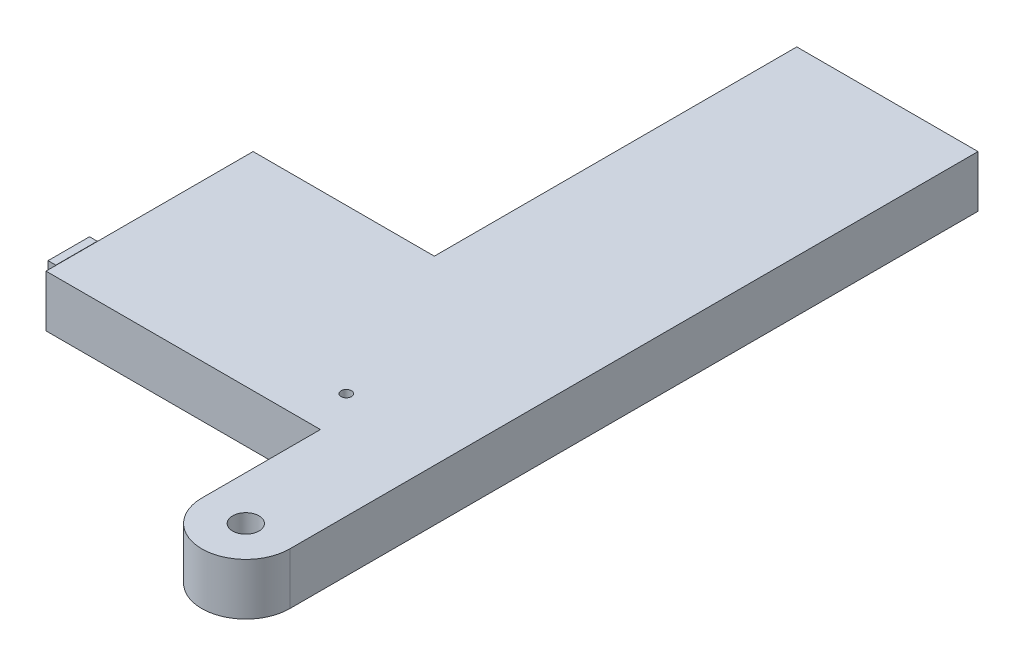
SolidWorks part; units mm, degrees
ref_plane "Front Plane" through (0, 0, 0) normal (0, 0, 1) x (1, 0, 0)
ref_plane "Top Plane" through (0, 0, 0) normal (0, 1, 0) x (1, 0, 0)
ref_plane "Right Plane" through (0, 0, 0) normal (1, 0, 0) x (0, 0, -1)
sketch "CornerrSketch1" plane through (0, 0, 0) normal (0, 1, 0) x (1, 0, 0)
  line L0 (0, 0) -> (0, 80)
  line L5 (0, 80) -> (70, 80)
  line L6 (70, 80) -> (70, 220)
  line L7 (140, 220) -> (70, 220)
  line L8 (106, -45.825) -> (106, 0)
  line L9 (0, 0) -> (106, 0)
  line L10 (140, 220) -> (140, -45.825)
  arc A0 (106, -45.825) -> (140, -45.825) centre (123, -45.825) ccw
  dimension "D5" = 34
  dimension "D4" = 80
  dimension "D3" = 70
  dimension "D1" = 220
  dimension "D2" = 45.825
  dimension "D6" = 140
extrude "CornerBoss-Extrude1" add sketch "CornerrSketch1" along normal blind 20
shell "Shell1" thickness 3 removed face at (79, 0, -61.4188)
sketch "PadSketch1" plane through (0, 17, 0) normal (0, -1, 0) x (1, 0, 0)
  line L1 (0, 0) -> (106, 0) construction
  line L2 (140, 45.825) -> (140, -220) construction
  circle A0 centre (99, -17) radius 5
  circle A1 centre (123, 45.825) radius 12
  dimension "D1" = 10
  dimension "D4" = 24
  dimension "D3" = 17
  dimension "D2" = 41
extrude "PadBoss-Extrude1" add sketch "PadSketch1" along normal blind 10
sketch "StepperShaftCut-Sketch3" plane through (0, 7, 0) normal (0, -1, 0) x (1, 0, 0)
  circle A0 centre (123, 45.825) radius 5.1
  circle A1 centre (99, -17) radius 2
  dimension "D1" = 10.2
  dimension "D2" = 4
extrude "StepperShaftCut-Extrude1" cut sketch "StepperShaftCut-Sketch3" against normal through all
sketch "ThreadedNutMountHolesSketch5" plane through (0, 7, 0) normal (0, -1, 0) x (1, 0, 0)
  circle A0 centre (123, 53.825) radius 1
  circle A1 centre (131, 45.825) radius 1
  circle A2 centre (115, 45.825) radius 1
  circle A3 centre (123, 37.825) radius 1
  dimension "D3" = 2
  dimension "D1" = 8
  dimension "D2" = 16
  dimension "D4" = 8
  dimension "D5" = 16
extrude "ThreadedNutMountHolesCut-Extrude2" cut sketch "ThreadedNutMountHolesSketch5" against normal blind 10
sketch "TopPegHoleSketch4" plane through (0, 0, -220) normal (0, 0, -1) x (-1, 0, 0)
  line L1 (-130, 14) -> (-120, 14)
  line L2 (-130, 14) -> (-130, 0)
  line L3 (-130, 0) -> (-120, 0)
  line L4 (-120, 14) -> (-120, 0)
  line L5 (-140, 0) -> (-70, 0) construction
  line L6 (-140, 20) -> (-140, 0) construction
  dimension "D2" = 10
  dimension "D3" = 14
  dimension "D1" = 10
extrude "TopPegHoleCut-Extrude2" cut sketch "TopPegHoleSketch4" against normal blind 3
sketch "BLPegSketch5" plane through (0, 0, 0) normal (-1, 0, 0) x (0, 0, 1)
  line L1 (-19.9, 13.9) -> (-10.1, 13.9)
  line L2 (-19.9, 13.9) -> (-19.9, 0)
  line L3 (-19.9, 0) -> (-10.1, 0)
  line L4 (-10.1, 13.9) -> (-10.1, 0)
  line L5 (-80, 0) -> (0, 0) construction
  line L6 (0, 20) -> (0, 0) construction
  dimension "D2" = 13.9
  dimension "D3" = 9.8
  dimension "D1" = 10.1
extrude "BLPegBoss-Extrude3" add sketch "BLPegSketch5" along normal blind 3.1
sketch "BLPegCapSketch6" plane through (-3.1, 0, 0) normal (-1, 0, 0) x (0, 0, 1)
  line L0 (-19.9, 13.9) -> (-19.9, 0) construction
  line L1 (-22.9, 17) -> (-6.9, 17)
  line L2 (-22.9, 17) -> (-22.9, 0)
  line L3 (-22.9, 0) -> (-6.9, 0)
  line L4 (-6.9, 17) -> (-6.9, 0)
  line L8 (-19.9, 0) -> (-10.1, 0) construction
  dimension "D1" = 16
  dimension "D3" = 17
  dimension "D2" = 3
extrude "BLPegCapBoss-Extrude4" add sketch "BLPegCapSketch6" along normal blind 3
sketch "BedCenterPegHoleCutSketch1" plane through (70, 0, 0) normal (-1, 0, 0) x (0, 0, 1)
  line L0 (-220, 0) -> (-80, 0) construction
  line L1 (-190, 14) -> (-180, 14)
  line L2 (-190, 14) -> (-190, 0)
  line L3 (-190, 0) -> (-180, 0)
  line L4 (-180, 14) -> (-180, 0)
  line L5 (-80, 20) -> (-80, 0) construction
  dimension "D2" = 10
  dimension "D1" = 14
  dimension "D3" = 100
extrude "BedCenterPegHoleCut-Extrude1" cut sketch "BedCenterPegHoleCutSketch1" against normal blind 3
equation "\"BedThickness\"= 20mm"
equation "\"BedToBuildPlateStandoffHolesDistanceFromLeftOrRight\"= \"BuildPlateStandoffHolesDistanceFromLeftOrRight\" + \"BedIncreasedByWidth\" / 2'Equals 17"
equation "\"BedLLongSide\"= \"BedThirdSize\" * 3'Equals 210"
equation "\"BedLShortSide\"= \"BedThirdSize\" * 2'Equals 140"
equation "\"BedLWidth\"= \"BedThirdSize\"'Equals 70"
equation "\"D4@CornerrSketch1\"=\"BedLWidth\" + \"BedIncreasedByWidth\"/2"
equation "\"BedIncreasedByWidth\"= 20mm"
equation "\"BedIncreasedByLength\"= 0mm"
equation "\"BedThirdSize\"= 70mm"
equation "\"StandardWallThickness\"= 3mm"
equation "\"D2@TopPegHoleSketch4\"=\"BedPegHoleWidth\""
equation "\"D3@TopPegHoleSketch4\"=\"BedPegHoleHeight\""
equation "\"D1@TopPegHoleCut-Extrude2\" = \"StandardWallThickness\""
equation "\"D3@BLPegSketch5\"=\"BedPegWidth\""
equation "\"D1@BLPegBoss-Extrude3\"=\"BedPegBoss\""
equation "\"D2@BLPegSketch5\"=\"BedPegHeight\""
equation "\"D2@BLPegCapSketch6\"=\"StandardWallThickness\""
equation "\"D3@BLPegCapSketch6\"=\"BedPegCapHeight\""
equation "\"D1@BLPegCapBoss-Extrude4\" = \"StandardWallThickness\""
equation "\"D3@CornerrSketch1\"=\"BedLWidth\" "
equation "\"D1@PadSketch1\" = \"BedToBuildPlateStandoffPadSize\""
equation "\"D1@PadBoss-Extrude1\"=\"LeadScrewNutPadDepth\""
equation "\"BedToBuildPlateStandoffPadSize\"= 10mm"
equation "\"BedToBuildPlateStandoffHolesDistanceFromBack\"= \"BuildPlateStandoffHolesDistanceFromBack\" + \"BedIncreasedByLength\" / 2'Equals 41"
equation "\"BuildPlateStandoffHolesDistanceFromLeftOrRight\"= 7mm"
equation "\"BuildPlateStandoffHolesDistanceFromBack\"= 41mm"
equation "\"DistanceFromBedSideToStepperHole\"= ( \"DistanceBetweenLeftToRightStepperHoles\" - \"BedWidth\" ) / 2'Equals 45.825"
equation "\"DistanceBetweenLeftToRightStepperHoles\"= \"FrontBackRailLength\" - \"StepperMountingHoleOffsetFromLeftOrRightSide\" * 2 - \"StepperMountingHoleDistance\"'Equals 461.65"
equation "\"FrontBackRailLength\"= 510mm"
equation "\"StepperMountingHoleOffsetFromLeftOrRightSide\"= \"StepperMountingHoleOffsetFromItsSide\" + \"RailThickness\""
equation "\"StepperMountingHoleDistance\"= 31mm'Spec"
equation "\"StepperMountingHoleOffsetFromItsSide\"= 5.5mm'Spec"
equation "\"RailThickness\"= .125in'Spec"
equation "\"BedWidth\"= \"BedInnerSquareWidth\" + \"BedLWidth\" * 2 + \"BedIncreasedByWidth\"'Equals 370"
equation "\"BedInnerSquareWidth\"= \"BedThirdSize\" * 3'Equals 210"
equation "\"D1@CornerrSketch1\"=\"BedLLongSide\"  + \"BedIncreasedByWidth\"/2"
equation "\"D2@CornerrSketch1\"=\"DistanceFromBedSideToStepperHole\""
equation "\"D3@PadSketch1\"=\"BedToBuildPlateStandoffHolesDistanceFromLeftOrRight\""
equation "\"D2@PadSketch1\"=\"BedToBuildPlateStandoffHolesDistanceFromBack\""
equation "\"D1@TopPegHoleSketch4\"=\"BedTopPegOffsetFromSide\""
equation "\"D1@BLPegSketch5\"=\"BedTopPegOffsetFromSide\" + .1mm"
equation "\"D6@CornerrSketch1\"=\"BedLShortSide\" + \"BedIncreasedByLength\"/2"
equation "\"LeadScrewNutPadSize\"= \"LeadScrewNutMountingHoleFlangeDiameter\" + 2mm'Equals 24"
equation "\"D4@PadSketch1\"=\"LeadScrewNutPadSize\""
equation "\"D1@StepperShaftCut-Sketch3\"=\"LeadScrewNutInnerShaftFlangeDiameter\""
equation "\"D2@StepperShaftCut-Sketch3\"=\"M3HeatInsertHoleDiameter\""
equation "\"LeadScrewNutInnerShaftFlangeDiameter\"= 10.2mm'Spec"
equation "\"LeadScrewNutMountHoleDiameter\"= 2mm'Spec is 4.1 but smaller for tapping"
equation "\"LeadScrewNutMountingHoleFlangeDiameter\"= 22mm'Spec"
equation "\"LeadScrewNutMountingHoleDistance\"= 16mm'Spec"
equation "\"D1@ThreadedNutMountHolesSketch5\"=\"LeadScrewNutMountingHoleDistance\"/2"
equation "\"D2@ThreadedNutMountHolesSketch5\"=\"LeadScrewNutMountingHoleDistance\""
equation "\"D4@ThreadedNutMountHolesSketch5\"=\"LeadScrewNutMountingHoleDistance\"/2"
equation "\"D5@ThreadedNutMountHolesSketch5\"=\"LeadScrewNutMountingHoleDistance\""
equation "\"D3@ThreadedNutMountHolesSketch5\"=\"LeadScrewNutMountHoleDiameter\""
equation "\"LeadScrewNutPadDepth\"= \"BedThickness\" / 2'Equals 10"
equation "\"D1@ThreadedNutMountHolesCut-Extrude2\"= \"LeadScrewNutPadDepth\""
equation "\"BedPegHoleWidth\"= 10mm"
equation "\"BedPegHoleHeight\"= \"BedThickness\" - \"StandardWallThickness\" * 2'Equals 14"
equation "\"BedPegWidth\"= \"BedPegHoleWidth\" - .1mm * 2'For easier assembly"
equation "\"BedPegHeight\"= \"BedPegHoleHeight\" - .1mm'For easier assembly"
equation "\"BedTopPegOffsetFromSide\"= 10mm"
equation "\"BedPegBoss\"= \"StandardWallThickness\" + .1mm'For easier assembly"
equation "\"BedPegCapHeight\"= \"BedThickness\" - \"StandardWallThickness\"'Equals 17"
equation "\"BedPegCapWidth\"= \"BedThickness\" / 2 + \"StandardWallThickness\" * 2'Equals 16"
equation "\"D1@BLPegCapSketch6\"=\"BedPegCapWidth\""
equation "\"D1@BedCenterPegHoleCutSketch1\" = \"BedPegHoleHeight\""
equation "\"D3@BedCenterPegHoleCutSketch1\" = \"BedInnerSquareWidth\" / 2 - \"BedPegHoleWidth\" / 2"
equation "\"D2@BedCenterPegHoleCutSketch1\" = \"BedPegHoleWidth\""
equation "\"D1@BedCenterPegHoleCut-Extrude1\"=\"StandardWallThickness\""
equation "\"M3HeatInsertHoleDiameter\"= 4mm'Spec"
